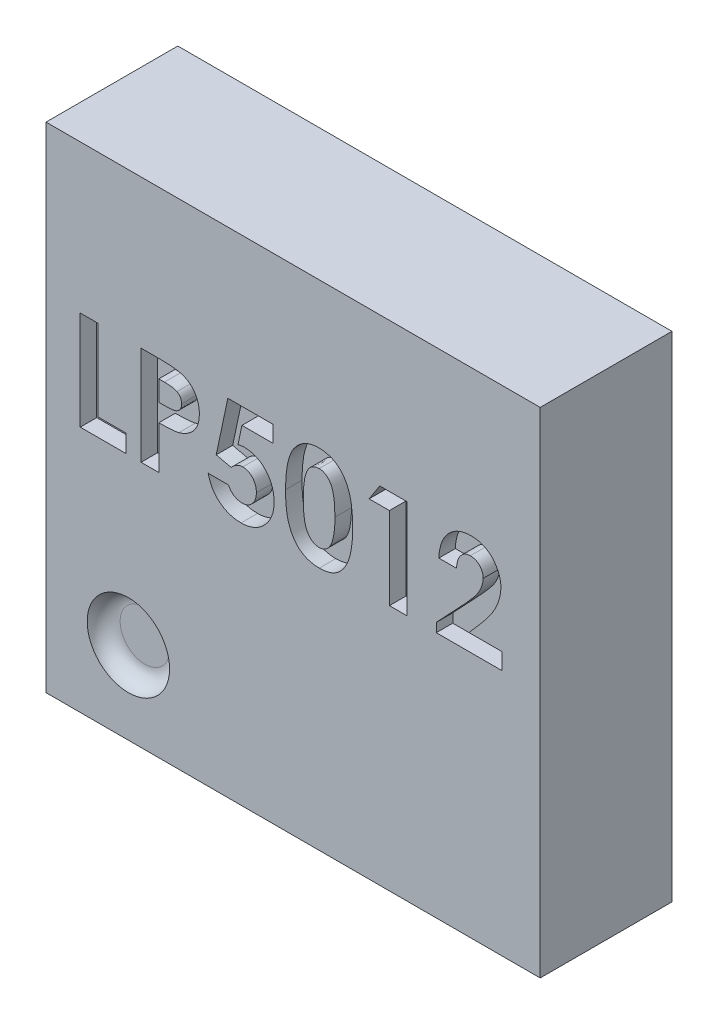
SolidWorks part; units mm, degrees
ref_plane "Alzado" through (0, 0, 0) normal (0, 0, 1) x (1, 0, 0)
ref_plane "Planta" through (0, 0, 0) normal (0, 1, 0) x (1, 0, 0)
ref_plane "Vista lateral" through (0, 0, 0) normal (1, 0, 0) x (0, 0, -1)
sketch "Croquis1" plane through (0, 0, 0) normal (0, 0, 1) x (1, 0, 0)
  line L1 (-1.5, -1.5) -> (1.5, -1.5)
  line L2 (-1.5, -1.5) -> (-1.5, 1.5)
  line L3 (-1.5, 1.5) -> (1.5, 1.5)
  line L4 (1.5, -1.5) -> (1.5, 1.5)
  line L5 (-1.5, -1.5) -> (1.5, 1.5) construction
  line L6 (-1.5, 1.5) -> (1.5, -1.5) construction
  point P0 (0, 0)
  dimension "D1" = 3
extrude "Saliente-Extruir1" add sketch "Croquis1" along normal blind 0.8
sketch "Croquis2" plane through (0, 0, 0.8) normal (0, 0, 1) x (1, 0, 0)
  line L0 (-1.5, -1.5) -> (1.5, -1.5) construction
  line L1 (-1.5, 1.5) -> (-1.5, -1.5) construction
  line L2 (-1.5, 0) -> (1.5, 0) construction
  line L3 (1.5, -1.5) -> (1.5, 1.5) construction
  circle A0 centre (-1, -1) radius 0.25
  text T0 "<b>LP5012</b>\r\n" font "Century Gothic" height 0.6
  dimension "D1" = 0.5
  dimension "D2" = 0.5
  dimension "D3" = 0.5
extrude "Cortar-Extruir1" cut sketch "Croquis2" against normal blind 0.1
fillet "Redondeo1" radius 0.1 1 edges at (-0.75, -1, 0.7)
